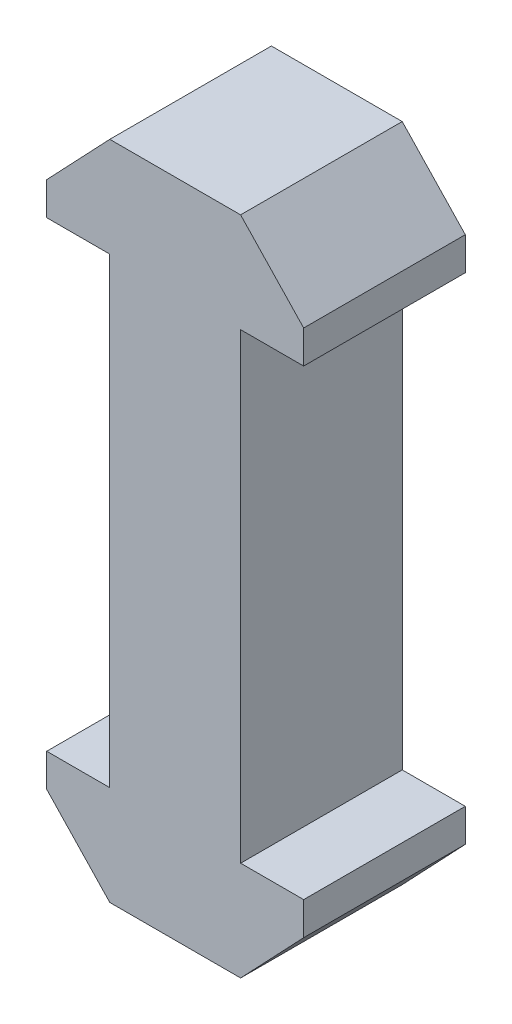
SolidWorks part; units mm, degrees
ref_plane "Front Plane" through (0, 0, 0) normal (0, 0, 1) x (1, 0, 0)
ref_plane "Top Plane" through (0, 0, 0) normal (0, 1, 0) x (1, 0, 0)
ref_plane "Right Plane" through (0, 0, 0) normal (1, 0, 0) x (0, 0, -1)
sketch "Sketch1" plane through (0, 0, 0) normal (0, 0, 1) x (1, 0, 0)
  line L3 (0, 0) -> (0, 14.2953) construction
  line L8 (0, 14.2953) -> (-8.6643, 14.2953) construction
  line L14 (-4.05, 0) -> (-4.05, 28.5906)
  line L15 (4.05, 0) -> (4.05, 28.5906)
  point P5 (-4.05, 14.2953)
  point P6 (4.05, 14.2953)
  line B0 (7.95, 0) -> (7.95, -2.04)
  line B1 (4.048, -6.1524) -> (-4.048, -6.1524)
  line B2 (-7.95, -2.04) -> (-7.95, 0)
  line B3 (-7.95, 0) -> (7.95, 0)
  line B4 (7.95, -2.04) -> (4.048, -6.1524)
  line B5 (-4.048, -6.1524) -> (-7.95, -2.04)
  line B6 (4.05, 0) -> (-4.05, 0) construction
  line B7 (7.95, 28.5906) -> (7.95, 30.6306)
  line B8 (4.048, 34.743) -> (-4.048, 34.743)
  line B9 (-7.95, 30.6306) -> (-7.95, 28.5906)
  line B10 (-7.95, 28.5906) -> (7.95, 28.5906)
  line B11 (7.95, 30.6306) -> (4.048, 34.743)
  line B12 (-4.048, 34.743) -> (-7.95, 30.6306)
  line B13 (4.05, 28.5906) -> (-4.05, 28.5906) construction
sketch_block_instance "Block1-1"
sketch_block "Block1" parameters "D1"=8.44, "D2"=2.6, "D3"=6, "D4"=16.7, "D6"=5.6686, "D7"=2.0404, "D8"=8.0963, "D9"=15.9, "D5"=2.4157
sketch_block_instance "Block1-5"
extrude "Boss-Extrude1" add sketch "Sketch1" along normal mid plane 10 contours B0 | B0 | B12 B9 B10 B7 B11 B8 | B10 L14 B3 L15 region at (0, -2.7416, 0) region at (0, 14.2953, 0) region at (0, 31.3322, 0)
equation "\"SmallJarHeight\"=65"
